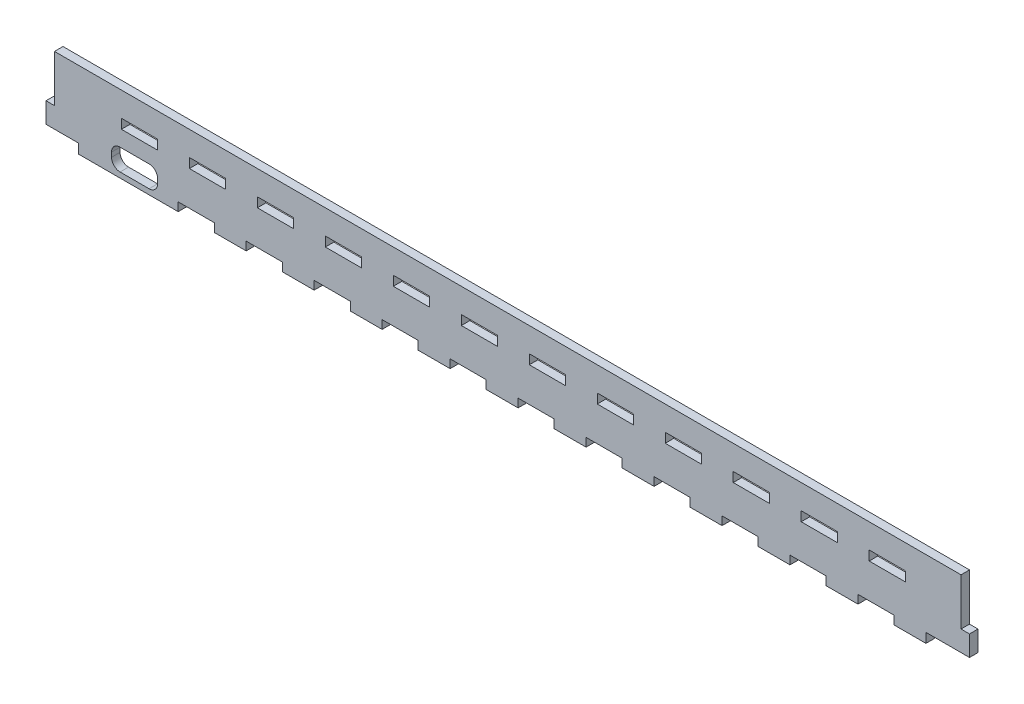
SolidWorks part; units mm, degrees
ref_plane "Plan de face" through (0, 0, 0) normal (0, 0, 1) x (1, 0, 0)
ref_plane "Plan de dessus" through (0, 0, 0) normal (0, 1, 0) x (1, 0, 0)
ref_plane "Plan de droite" through (0, 0, 0) normal (1, 0, 0) x (0, 0, -1)
sketch "Esquisse1" plane through (0, 0, 0) normal (0, 0, 1) x (1, 0, 0)
  line L1 (-108.68, -6.055) -> (108.68, -6.055)
  line L2 (-108.68, -6.055) -> (-108.68, 6.055)
  line L3 (-108.68, 6.055) -> (108.68, 6.055)
  line L4 (108.68, -6.055) -> (108.68, 6.055)
  line L5 (-108.68, -6.055) -> (108.68, 6.055) construction
  line L6 (-108.68, 6.055) -> (108.68, -6.055) construction
  point P0 (0, 0)
extrude "Boss.-Extru.1" add sketch "Esquisse1" along normal blind 2
sketch "Esquisse2" plane through (0, 0, 2) normal (0, 0, 1) x (1, 0, 0)
  line L1 (-109.57, -4.055) -> (-108.68, -4.055)
  line L2 (-109.57, -4.055) -> (-109.57, -6.055)
  line L3 (-109.57, -6.055) -> (-101.07, -6.055)
  line L4 (-101.07, -4.055) -> (-101.07, -6.055)
  line L5 (-90.93, 4.055) -> (-82.43, 4.055)
  line L6 (-90.93, 4.055) -> (-90.93, 6.055)
  line L7 (-90.93, 6.055) -> (-82.43, 6.055)
  line L8 (-82.43, 4.055) -> (-82.43, 6.055)
  line L9 (-108.68, -4.055) -> (-101.32, -4.055) construction
  line L10 (-101.32, -6.055) -> (-108.68, -6.055) construction
  line L12 (-90.68, 4.055) -> (-82.68, 4.055) construction
  line L13 (-90.68, 6.055) -> (-82.68, 6.055) construction
  line L22 (-77.57, -4.055) -> (-69.07, -4.055)
  line L23 (-77.57, -4.055) -> (-77.57, -6.055)
  line L24 (-77.57, -6.055) -> (-69.07, -6.055)
  line L25 (-69.07, -4.055) -> (-69.07, -6.055)
  line L30 (-61.57, -4.055) -> (-53.07, -4.055)
  line L31 (-61.57, -4.055) -> (-61.57, -6.055)
  line L32 (-61.57, -6.055) -> (-53.07, -6.055)
  line L33 (-53.07, -4.055) -> (-53.07, -6.055)
  line L38 (-45.57, -4.055) -> (-37.07, -4.055)
  line L39 (-45.57, -4.055) -> (-45.57, -6.055)
  line L40 (-45.57, -6.055) -> (-37.07, -6.055)
  line L41 (-37.07, -4.055) -> (-37.07, -6.055)
  line L46 (-29.57, -4.055) -> (-21.07, -4.055)
  line L47 (-29.57, -4.055) -> (-29.57, -6.055)
  line L48 (-29.57, -6.055) -> (-21.07, -6.055)
  line L49 (-21.07, -4.055) -> (-21.07, -6.055)
  line L54 (-13.57, -4.055) -> (-5.07, -4.055)
  line L55 (-13.57, -4.055) -> (-13.57, -6.055)
  line L56 (-13.57, -6.055) -> (-5.07, -6.055)
  line L57 (-5.07, -4.055) -> (-5.07, -6.055)
  line L62 (2.43, -4.055) -> (10.93, -4.055)
  line L63 (2.43, -4.055) -> (2.43, -6.055)
  line L64 (2.43, -6.055) -> (10.93, -6.055)
  line L65 (10.93, -4.055) -> (10.93, -6.055)
  line L70 (18.43, -4.055) -> (26.93, -4.055)
  line L71 (18.43, -4.055) -> (18.43, -6.055)
  line L72 (18.43, -6.055) -> (26.93, -6.055)
  line L73 (26.93, -4.055) -> (26.93, -6.055)
  line L78 (34.43, -4.055) -> (42.93, -4.055)
  line L79 (34.43, -4.055) -> (34.43, -6.055)
  line L80 (34.43, -6.055) -> (42.93, -6.055)
  line L81 (42.93, -4.055) -> (42.93, -6.055)
  line L86 (50.43, -4.055) -> (58.93, -4.055)
  line L87 (50.43, -4.055) -> (50.43, -6.055)
  line L88 (50.43, -6.055) -> (58.93, -6.055)
  line L89 (58.93, -4.055) -> (58.93, -6.055)
  line L94 (66.43, -4.055) -> (74.93, -4.055)
  line L95 (66.43, -4.055) -> (66.43, -6.055)
  line L96 (66.43, -6.055) -> (74.93, -6.055)
  line L97 (74.93, -4.055) -> (74.93, -6.055)
  line L102 (82.43, -4.055) -> (90.93, -4.055)
  line L103 (82.43, -4.055) -> (82.43, -6.055)
  line L104 (82.43, -6.055) -> (90.93, -6.055)
  line L105 (90.93, -4.055) -> (90.93, -6.055)
  line L110 (101.07, 4.055) -> (109.57, 4.055) [skipped]
  line L111 (101.07, 4.055) -> (101.07, 6.055) [skipped]
  line L112 (101.07, 6.055) -> (109.57, 6.055) [skipped]
  line L113 (109.57, 4.055) -> (109.57, 6.055) [skipped]
  line L114 (-77.32, -6.055) -> (-77.32, -4.055) construction
  line L115 (-69.32, -4.055) -> (-69.32, -6.055) construction
  line L117 (-74.93, 4.055) -> (-66.43, 4.055) [skipped]
  line L118 (-74.93, 4.055) -> (-74.93, 6.055) [skipped]
  line L119 (-74.93, 6.055) -> (-66.43, 6.055) [skipped]
  line L120 (-66.43, 4.055) -> (-66.43, 6.055) [skipped]
  line L121 (-58.93, 4.055) -> (-50.43, 4.055) [skipped]
  line L122 (-58.93, 4.055) -> (-58.93, 6.055) [skipped]
  line L123 (-58.93, 6.055) -> (-50.43, 6.055) [skipped]
  line L124 (-50.43, 4.055) -> (-50.43, 6.055) [skipped]
  line L125 (-42.93, 4.055) -> (-34.43, 4.055) [skipped]
  line L126 (-42.93, 4.055) -> (-42.93, 6.055) [skipped]
  line L127 (-42.93, 6.055) -> (-34.43, 6.055) [skipped]
  line L128 (-34.43, 4.055) -> (-34.43, 6.055) [skipped]
  line L129 (-26.93, 4.055) -> (-18.43, 4.055) [skipped]
  line L130 (-26.93, 4.055) -> (-26.93, 6.055) [skipped]
  line L131 (-26.93, 6.055) -> (-18.43, 6.055) [skipped]
  line L132 (-18.43, 4.055) -> (-18.43, 6.055) [skipped]
  line L133 (-10.93, 4.055) -> (-2.43, 4.055) [skipped]
  line L134 (-10.93, 4.055) -> (-10.93, 6.055) [skipped]
  line L135 (-10.93, 6.055) -> (-2.43, 6.055) [skipped]
  line L136 (-2.43, 4.055) -> (-2.43, 6.055) [skipped]
  line L137 (5.07, 4.055) -> (13.57, 4.055) [skipped]
  line L138 (5.07, 4.055) -> (5.07, 6.055) [skipped]
  line L139 (5.07, 6.055) -> (13.57, 6.055) [skipped]
  line L140 (13.57, 4.055) -> (13.57, 6.055) [skipped]
  line L141 (21.07, 4.055) -> (29.57, 4.055) [skipped]
  line L142 (21.07, 4.055) -> (21.07, 6.055) [skipped]
  line L143 (21.07, 6.055) -> (29.57, 6.055) [skipped]
  line L144 (29.57, 4.055) -> (29.57, 6.055) [skipped]
  line L145 (37.07, 4.055) -> (45.57, 4.055) [skipped]
  line L146 (37.07, 4.055) -> (37.07, 6.055) [skipped]
  line L147 (37.07, 6.055) -> (45.57, 6.055) [skipped]
  line L148 (45.57, 4.055) -> (45.57, 6.055) [skipped]
  line L149 (53.07, 4.055) -> (61.57, 4.055) [skipped]
  line L150 (53.07, 4.055) -> (53.07, 6.055) [skipped]
  line L151 (53.07, 6.055) -> (61.57, 6.055) [skipped]
  line L152 (61.57, 4.055) -> (61.57, 6.055) [skipped]
  line L153 (69.07, 4.055) -> (77.57, 4.055) [skipped]
  line L154 (69.07, 4.055) -> (69.07, 6.055) [skipped]
  line L155 (69.07, 6.055) -> (77.57, 6.055) [skipped]
  line L156 (77.57, 4.055) -> (77.57, 6.055) [skipped]
  line L157 (85.07, 4.055) -> (93.57, 4.055) [skipped]
  line L158 (85.07, 4.055) -> (85.07, 6.055) [skipped]
  line L159 (85.07, 6.055) -> (93.57, 6.055) [skipped]
  line L160 (93.57, 4.055) -> (93.57, 6.055) [skipped]
  line L161 (-82.68, 4.055) -> (-82.68, 6.055) construction
  line L162 (-74.93, 4.055) -> (-66.43, 4.055)
  line L163 (-74.93, 4.055) -> (-74.93, 6.055)
  line L164 (-74.93, 6.055) -> (-66.43, 6.055)
  line L165 (-66.43, 4.055) -> (-66.43, 6.055)
  line L166 (-58.93, 4.055) -> (-50.43, 4.055)
  line L167 (-58.93, 4.055) -> (-58.93, 6.055)
  line L168 (-58.93, 6.055) -> (-50.43, 6.055)
  line L169 (-50.43, 4.055) -> (-50.43, 6.055)
  line L170 (-42.93, 4.055) -> (-34.43, 4.055)
  line L171 (-42.93, 4.055) -> (-42.93, 6.055)
  line L172 (-42.93, 6.055) -> (-34.43, 6.055)
  line L173 (-34.43, 4.055) -> (-34.43, 6.055)
  line L174 (-26.93, 4.055) -> (-18.43, 4.055)
  line L175 (-26.93, 4.055) -> (-26.93, 6.055)
  line L176 (-26.93, 6.055) -> (-18.43, 6.055)
  line L177 (-18.43, 4.055) -> (-18.43, 6.055)
  line L178 (-10.93, 4.055) -> (-2.43, 4.055)
  line L179 (-10.93, 4.055) -> (-10.93, 6.055)
  line L180 (-10.93, 6.055) -> (-2.43, 6.055)
  line L181 (-2.43, 4.055) -> (-2.43, 6.055)
  line L182 (5.07, 4.055) -> (13.57, 4.055)
  line L183 (5.07, 4.055) -> (5.07, 6.055)
  line L184 (5.07, 6.055) -> (13.57, 6.055)
  line L185 (13.57, 4.055) -> (13.57, 6.055)
  line L186 (21.07, 4.055) -> (29.57, 4.055)
  line L187 (21.07, 4.055) -> (21.07, 6.055)
  line L188 (21.07, 6.055) -> (29.57, 6.055)
  line L189 (29.57, 4.055) -> (29.57, 6.055)
  line L190 (37.07, 4.055) -> (45.57, 4.055)
  line L191 (37.07, 4.055) -> (37.07, 6.055)
  line L192 (37.07, 6.055) -> (45.57, 6.055)
  line L193 (45.57, 4.055) -> (45.57, 6.055)
  line L194 (53.07, 4.055) -> (61.57, 4.055)
  line L195 (53.07, 4.055) -> (53.07, 6.055)
  line L196 (53.07, 6.055) -> (61.57, 6.055)
  line L197 (61.57, 4.055) -> (61.57, 6.055)
  line L198 (69.07, 4.055) -> (77.57, 4.055)
  line L199 (69.07, 4.055) -> (69.07, 6.055)
  line L200 (69.07, 6.055) -> (77.57, 6.055)
  line L201 (77.57, 4.055) -> (77.57, 6.055)
  line L202 (85.07, 4.055) -> (93.57, 4.055)
  line L203 (85.07, 4.055) -> (85.07, 6.055)
  line L204 (85.07, 6.055) -> (93.57, 6.055)
  line L205 (93.57, 4.055) -> (93.57, 6.055)
  line L206 (93.32, 4.055) -> (93.32, 6.055) construction
  line L207 (90.68, -4.055) -> (90.68, -6.055) construction
  line L208 (82.68, -4.055) -> (90.68, -4.055) construction
  line L209 (-108.68, -6.055) -> (108.68, -6.055) construction
  line L210 (98.43, -6.055) -> (108.68, -6.055)
  line L211 (98.43, -6.055) -> (98.43, -3.805)
  line L212 (98.43, -3.805) -> (108.68, -3.805)
  line L213 (108.68, -6.055) -> (108.68, -3.805)
  line L214 (108.68, -6.055) -> (108.68, 6.055) construction
  line L215 (108.68, -4.055) -> (98.68, -4.055) construction
  line L216 (98.68, -6.055) -> (98.68, -4.055) construction
  line L218 (-108.68, -4.055) -> (-101.07, -4.055) construction
  line L219 (-108.68, -4.055) -> (-108.68, -3.805)
  line L220 (-108.68, -3.805) -> (-101.07, -3.805)
  line L221 (-101.07, -4.055) -> (-101.07, -3.805)
  line L223 (-108.68, -4.055) -> (-101.07, -4.055) construction
  line L224 (-93.57, -4.055) -> (-85.07, -4.055) [skipped]
  line L225 (-93.57, -4.055) -> (-93.57, -6.055) [skipped]
  line L226 (-93.57, -6.055) -> (-85.07, -6.055) [skipped]
  line L227 (-85.07, -4.055) -> (-85.07, -6.055) [skipped]
  point P3 (-89, -4.055)
  point P8 (-105, -4.055)
  point P17 (-86.68, 4.055)
  point P24 (105.32, 4.055)
  point P28 (89.32, 4.055)
  point P29 (73.32, 4.055)
  point P30 (57.32, 4.055)
  point P31 (41.32, 4.055)
  point P38 (25.32, 4.055)
  point P39 (9.32, 4.055)
  point P40 (-6.68, 4.055)
  point P41 (-22.68, 4.055)
  point P42 (-73, -4.055)
  point P43 (-70.68, 4.055)
  point P48 (-38.68, 4.055)
  point P49 (-54.68, 4.055)
  point P52 (-57, -4.055)
  point P58 (-70.68, 4.055)
  point P62 (-41, -4.055)
  point P68 (-54.68, 4.055)
  point P72 (-25, -4.055)
  point P78 (-38.68, 4.055)
  point P82 (-9, -4.055)
  point P88 (-22.68, 4.055)
  point P92 (7, -4.055)
  point P98 (-6.68, 4.055)
  point P102 (23, -4.055)
  point P108 (9.32, 4.055)
  point P112 (39, -4.055)
  point P118 (25.32, 4.055)
  point P122 (55, -4.055)
  point P128 (41.32, 4.055)
  point P132 (71, -4.055)
  point P141 (57.32, 4.055)
  point P142 (87, -4.055)
  point P243 (73.32, 4.055)
  point P248 (89.32, 4.055)
  dimension "D1" = 0.25
  dimension "D2" = 0.25
  dimension "D4" = 0.25
  dimension "D6" = 0.25
  dimension "D7" = 0.25
  dimension "D8" = 0.25
  dimension "D9" = 0.25
  dimension "D10" = 0.25
  dimension "D3" = 13
  dimension "D5" = 12
extrude "Enlèv. mat.-Extru.1" cut sketch "Esquisse2" against normal through all
sketch "Esquisse3" plane through (0, 0, 2) normal (0, 0, 1) x (1, 0, 0)
  line L0 (-93.002, -1.925) -> (-93.002, -2.625) construction
  line L1 (-91.252, 0.255) -> (-84.412, 0.255)
  line L2 (-93.252, -1.745) -> (-93.252, -2.805)
  line L3 (-91.252, -4.805) -> (-84.412, -4.805)
  line L4 (-82.412, -1.745) -> (-82.412, -2.805)
  line L5 (-82.662, -2.625) -> (-82.662, -1.925) construction
  line L6 (-84.592, 0.005) -> (-91.072, 0.005) construction
  line L7 (-91.072, -4.555) -> (-84.592, -4.555) construction
  arc A0 (-93.252, -2.805) -> (-91.252, -4.805) centre (-91.252, -2.805) ccw
  arc A1 (-84.412, 0.255) -> (-82.412, -1.745) centre (-84.412, -1.745) cw
  arc A2 (-84.412, -4.805) -> (-82.412, -2.805) centre (-84.412, -2.805) ccw
  arc A3 (-91.252, 0.255) -> (-93.252, -1.745) centre (-91.252, -1.745) ccw
  dimension "D5" = 2
  dimension "D1" = 0.25
  dimension "D2" = 0.25
  dimension "D3" = 0.25
  dimension "D4" = 0.25
extrude "Enlèv. mat.-Extru.2" cut sketch "Esquisse3" against normal through all
sketch "Esquisse5" plane through (0, 0, 2) normal (0, 0, 1) x (1, 0, 0)
  line L0 (0, 0) -> (0, -11.5957) construction
  line L1 (-108.68, 1) -> (-106.68, 1)
  line L2 (-108.68, 1) -> (-108.68, 6.055)
  line L3 (-108.68, 6.055) -> (-106.68, 6.055)
  line L4 (-106.68, 1) -> (-106.68, 6.055)
  line L5 (106.68, 1) -> (106.68, 6.055)
  line L6 (108.68, 6.055) -> (106.68, 6.055)
  line L7 (108.68, 1) -> (108.68, 6.055)
  line L8 (108.68, 1) -> (106.68, 1)
extrude "Enlèv. mat.-Extru.3" cut sketch "Esquisse5" against normal through all
sketch "Esquisse6" plane through (0, 0, 2) normal (0, 0, 1) x (1, 0, 0)
  line L1 (-106.68, 6.055) -> (106.68, 6.055)
  line L2 (-106.68, 6.055) -> (-106.68, 12.055)
  line L3 (-106.68, 12.055) -> (106.68, 12.055)
  line L4 (106.68, 6.055) -> (106.68, 12.055)
  point P5 (106.68, 6.055)
  point P7 (-106.68, 12.055)
extrude "Boss.-Extru.2" add sketch "Esquisse6" against normal up to surface (2 mm away) up to face at (3.3846, 0.0865, 0)
sketch "Esquisse7" plane through (0, 0, 2) normal (0, 0, 1) x (1, 0, 0)
  line L0 (-74.93, 6.055) -> (-66.43, 6.055)
  line L1 (-90.93, 6.055) -> (-82.43, 6.055)
  line L2 (-90.93, 6.055) -> (-90.93, 6.305)
  line L3 (-90.93, 6.305) -> (-82.43, 6.305)
  line L4 (-82.43, 6.055) -> (-82.43, 6.305)
  line L5 (-74.93, 6.055) -> (-74.93, 6.305)
  line L6 (-74.93, 6.305) -> (-66.43, 6.305)
  line L7 (-66.43, 6.055) -> (-66.43, 6.305)
  line L8 (-58.93, 6.055) -> (-50.43, 6.055)
  line L9 (-58.93, 6.055) -> (-58.93, 6.305)
  line L10 (-58.93, 6.305) -> (-50.43, 6.305)
  line L11 (-50.43, 6.055) -> (-50.43, 6.305)
  line L12 (-42.93, 6.055) -> (-34.43, 6.055)
  line L13 (-42.93, 6.055) -> (-42.93, 6.305)
  line L14 (-42.93, 6.305) -> (-34.43, 6.305)
  line L15 (-34.43, 6.055) -> (-34.43, 6.305)
  line L16 (-26.93, 6.055) -> (-18.43, 6.055)
  line L17 (-26.93, 6.055) -> (-26.93, 6.305)
  line L18 (-26.93, 6.305) -> (-18.43, 6.305)
  line L19 (-18.43, 6.055) -> (-18.43, 6.305)
  line L20 (-10.93, 6.055) -> (-2.43, 6.055)
  line L21 (-10.93, 6.055) -> (-10.93, 6.305)
  line L22 (-10.93, 6.305) -> (-2.43, 6.305)
  line L23 (-2.43, 6.055) -> (-2.43, 6.305)
  line L24 (5.07, 6.055) -> (13.57, 6.055)
  line L25 (5.07, 6.055) -> (5.07, 6.305)
  line L26 (5.07, 6.305) -> (13.57, 6.305)
  line L27 (13.57, 6.055) -> (13.57, 6.305)
  line L28 (21.07, 6.055) -> (29.57, 6.055)
  line L29 (21.07, 6.055) -> (21.07, 6.305)
  line L30 (21.07, 6.305) -> (29.57, 6.305)
  line L31 (29.57, 6.055) -> (29.57, 6.305)
  line L32 (37.07, 6.055) -> (45.57, 6.055)
  line L33 (37.07, 6.055) -> (37.07, 6.305)
  line L34 (37.07, 6.305) -> (45.57, 6.305)
  line L35 (45.57, 6.055) -> (45.57, 6.305)
  line L36 (53.07, 6.055) -> (61.57, 6.055)
  line L37 (53.07, 6.055) -> (53.07, 6.305)
  line L38 (53.07, 6.305) -> (61.57, 6.305)
  line L39 (61.57, 6.055) -> (61.57, 6.305)
  line L40 (69.07, 6.055) -> (77.57, 6.055)
  line L41 (69.07, 6.055) -> (69.07, 6.305)
  line L42 (69.07, 6.305) -> (77.57, 6.305)
  line L43 (77.57, 6.055) -> (77.57, 6.305)
  line L44 (85.07, 6.055) -> (93.57, 6.055)
  line L45 (85.07, 6.055) -> (85.07, 6.305)
  line L46 (85.07, 6.305) -> (93.57, 6.305)
  line L47 (93.57, 6.055) -> (93.57, 6.305)
  line L48 (85.07, 6.055) -> (93.57, 6.055) construction
  point P8 (93.5698, 6.055)
  point P54 (93.3717, 6.305)
  point P55 (0, 0)
  point P56 (93.57, 6.055)
  dimension "D1" = 0.25
  dimension "D2" = 12
extrude "Enlèv. mat.-Extru.4" cut sketch "Esquisse7" against normal through all
